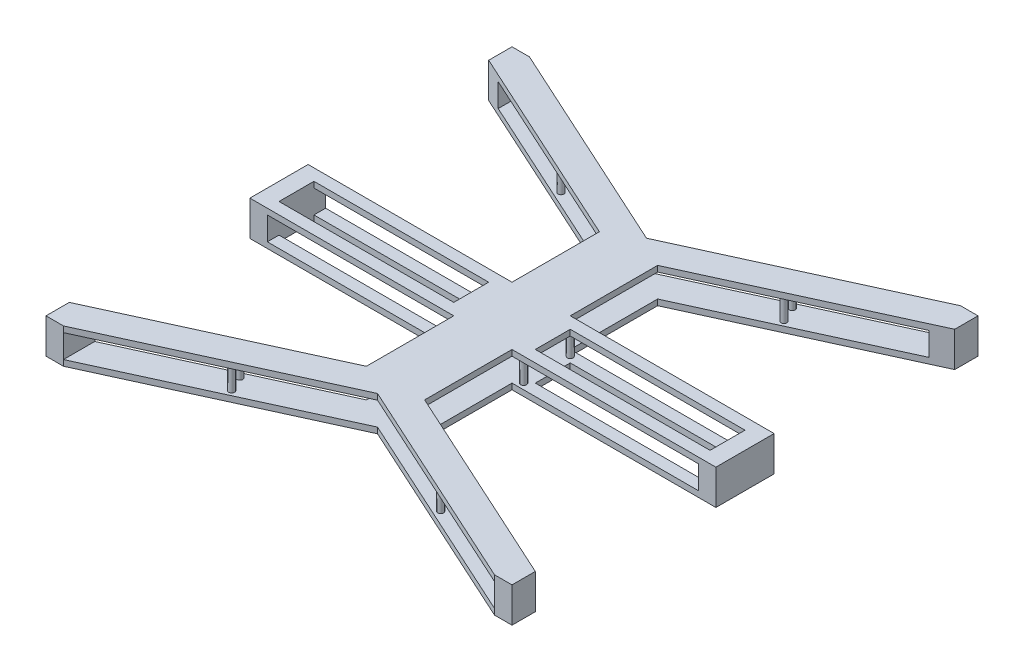
SolidWorks part; units mm, degrees
ref_plane "Front Plane" through (0, 0, 0) normal (0, 0, 1) x (1, 0, 0)
ref_plane "Top Plane" through (0, 0, 0) normal (0, 1, 0) x (1, 0, 0)
ref_plane "Right Plane" through (0, 0, 0) normal (1, 0, 0) x (0, 0, -1)
sketch "Sketch1" plane through (0, 0, 0) normal (0, 1, 0) x (1, 0, 0)
  line L1 (-13.2, 0) -> (13.2, 0) construction
  line L2 (80, 10) -> (80, -10)
  line L3 (80, -10) -> (10, -10)
  line L4 (10, -10) -> (10, -40)
  line L5 (10, -40) -> (80, -72)
  line L6 (80, -72) -> (80, -80)
  line L7 (80, -80) -> (74, -80)
  line L8 (74, -80) -> (0, -46.1714)
  line L9 (0, -13.2) -> (0, 13.2) construction
  line L11 (-80, 10) -> (-80, -10)
  line L12 (-80, -10) -> (-10, -10)
  line L13 (-10, -10) -> (-10, -40)
  line L14 (-10, -40) -> (-80, -72)
  line L15 (-80, -72) -> (-80, -80)
  line L16 (-80, -80) -> (-74, -80)
  line L17 (-74, -80) -> (0, -46.1714)
  line L18 (80, 10) -> (10, 10)
  line L19 (10, 10) -> (10, 40)
  line L20 (80, 80) -> (74, 80)
  line L21 (80, 72) -> (80, 80)
  line L22 (10, 40) -> (80, 72)
  line L23 (74, 80) -> (0, 46.1714)
  line L24 (-80, 72) -> (-80, 80)
  line L25 (-80, 80) -> (-74, 80)
  line L26 (-74, 80) -> (0, 46.1714)
  line L27 (-10, 40) -> (-80, 72)
  line L28 (-80, 10) -> (-10, 10)
  line L29 (-10, 10) -> (-10, 40)
  point P21 (80, 0)
  point P33 (-80, 0)
  dimension "D3" = 10
  dimension "D5" = 8
  dimension "D6" = 30
  dimension "D8" = 6
  dimension "D1" = 80
  dimension "D2" = 80
  dimension "D4" = 80
  dimension "D7" = 10
extrude "Boss-Extrude1" add sketch "Sketch1" along normal blind 6 and the other way blind 6
sketch "Sketch2" plane through (0, 0, 80) normal (0, 0, 1) x (1, 0, 0)
  line L0 (-74, -6) -> (-74, 6) construction
  line L1 (-74, -4) -> (74, -4)
  line L2 (-74, -4) -> (-74, 4)
  line L3 (-74, 4) -> (74, 4)
  line L4 (74, -4) -> (74, 4)
  line L5 (74, -6) -> (74, 6) construction
  line L7 (176, 0) -> (-176, 0) construction
  dimension "D1" = 4
  dimension "D2" = 4
extrude "Cut-Extrude1" cut sketch "Sketch2" against normal blind 160
sketch "Sketch4" plane through (0, 6, 0) normal (0, 1, 0) x (1, 0, 0)
  line L0 (-13.2, 0) -> (13.2, 0) construction
  line L1 (-74, 6) -> (-14, 6)
  line L2 (-74, 6) -> (-74, -6)
  line L3 (-74, -6) -> (-14, -6)
  line L4 (-14, 6) -> (-14, -6)
  line L5 (-80, 10) -> (-80, -10) construction
  line L7 (0, -13.2) -> (0, 13.2) construction
  line L8 (74, -6) -> (14, -6)
  line L9 (14, 6) -> (14, -6)
  line L10 (74, 6) -> (14, 6)
  line L11 (74, 6) -> (74, -6)
  dimension "D1" = 6
  dimension "D2" = 6
  dimension "D3" = 6
  dimension "D4" = 60
extrude "Cut-Extrude2" cut sketch "Sketch4" against normal blind 12
sketch "Sketch5" plane through (0, -4, 0) normal (0, 1, 0) x (1, 0, 0)
  line L1 (-10, -40) -> (-74, -69.2571) construction
  line L2 (-74, -80) -> (0, -46.1714) construction
  line L4 (-39.1032, -53.3043) -> (-35.0411, -62.1902) construction
  line L5 (0, -13.2) -> (0, 13.2) construction
  line L6 (-14, 6) -> (-14, -6) construction
  line L7 (-14, -6) -> (-74, -6) construction
  line L8 (-13.2, 0) -> (13.2, 0) construction
  circle A0 centre (-35.8726, -60.3713) radius 1
  circle A1 centre (-38.2717, -55.1233) radius 1
  circle A3 centre (-12, -8) radius 1
  circle A4 centre (0, -40.1714) radius 1
  circle A5 centre (12, -8) radius 1
  circle A6 centre (35.8726, -60.3713) radius 1
  circle A7 centre (38.2717, -55.1233) radius 1
  circle A8 centre (38.2717, 55.1233) radius 1
  circle A9 centre (35.8726, 60.3713) radius 1
  circle A10 centre (-35.8726, 60.3713) radius 1
  circle A11 centre (-38.2717, 55.1233) radius 1
  circle A12 centre (0, 40.1714) radius 1
  circle A13 centre (12, 8) radius 1
  circle A14 centre (-12, 8) radius 1
  dimension "D1" = 2
  dimension "D2" = 2
  dimension "D4" = 2
  dimension "D3" = 2
  dimension "D6" = 2
  dimension "D8" = 32
  dimension "D5" = 2
  dimension "D7" = 90
  dimension "D9" = 6
  dimension "D10" = 2
  dimension "D11" = 2
extrude "Boss-Extrude2" add sketch "Sketch5" along normal blind 8
equation "\"A\" = 2"
equation "\"D5@Sketch1\"=4*\"A\""
equation "\"D6@Sketch1\"=15*\"A\""
equation "\"D8@Sketch1\"=3*\"A\""
equation "\"D1@Sketch1\"=40*\"A\""
equation "\"D2@Sketch1\"=40*\"A\""
equation "\"D4@Sketch1\"=40*\"A\""
equation "\"D7@Sketch1\"=5*\"A\""
equation "\"D1@Boss-Extrude1\"=3*\"A\""
equation "\"D2@Boss-Extrude1\"=3*\"A\""
equation "\"D1@Sketch2\"=2*\"A\""
equation "\"D2@Sketch2\"=2*\"A\""
equation "\"D1@Sketch4\"=3*\"A\""
equation "\"D2@Sketch4\"=3*\"A\""
equation "\"D3@Sketch4\"=3*\"A\""
equation "\"D4@Sketch4\"=30*\"A\""
equation "\"D1@Cut-Extrude2\"=6*\"A\""
equation "\"D1@Cut-Extrude1\"=80*\"A\""
equation "\"D3@Sketch1\"=5*\"A\""
equation "\"D1@Sketch5\"=\"A\""
equation "\"D2@Sketch5\"=\"A\""
equation "\"D4@Sketch5\"=\"A\""
equation "\"D6@Sketch5\"=\"A\""
equation "\"D8@Sketch5\"=16*\"A\""
equation "\"D5@Sketch5\"=\"A\""
equation "\"D3@Sketch5\"=\"A\""
equation "\"D9@Sketch5\"=3*\"A\""
equation "\"D10@Sketch5\"=\"A\""
equation "\"D11@Sketch5\"=\"A\""
equation "\"D1@Boss-Extrude2\"=4*\"A\""
